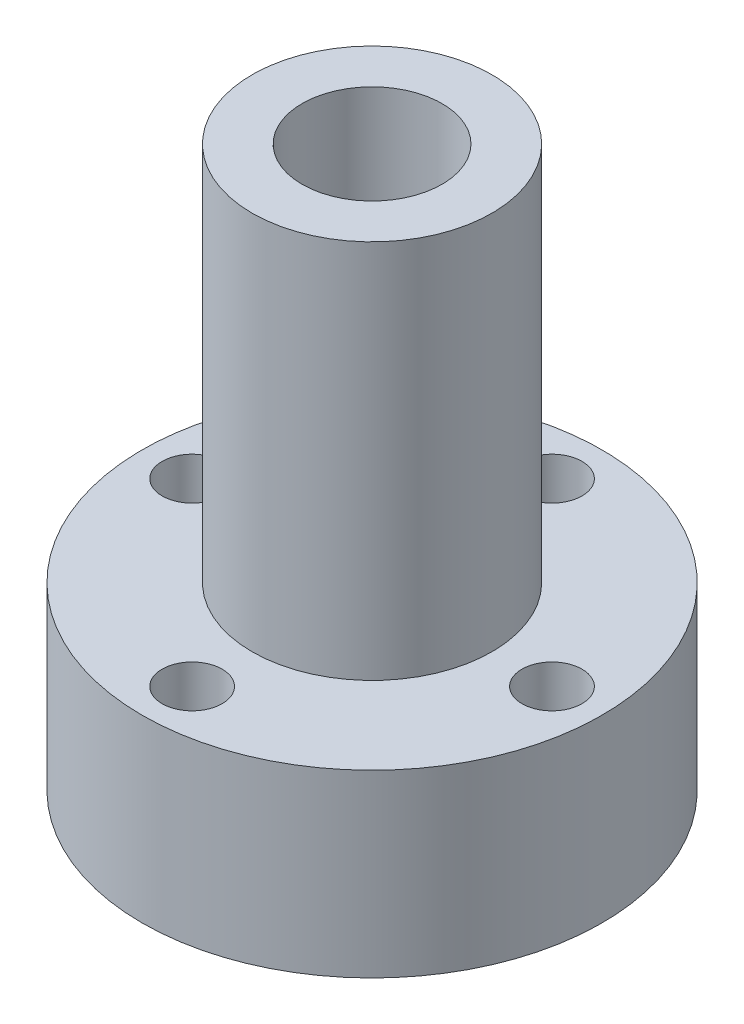
SolidWorks part; units mm, degrees
material "1023 Arkusz stali węglowej (SS)"
ref_plane "Płaszczyzna przednia" through (0, 0, 0) normal (0, 0, 1) x (1, 0, 0)
ref_plane "Płaszczyzna górna" through (0, 0, 0) normal (0, 1, 0) x (1, 0, 0)
ref_plane "Płaszczyzna prawa" through (0, 0, 0) normal (1, 0, 0) x (0, 0, -1)
sketch "Szkic1" plane through (0, 0, 0) normal (0, 0, 1) x (1, 0, 0)
  line L0 (0, 0) -> (0, -37.7643) construction
  line L10 (-23, -9.5) -> (-12, -9.5)
  line L11 (-12, -9.5) -> (-12, 28.5)
  line L12 (-7, 28.5) -> (-7, -29.5)
  line L13 (-7, 28.5) -> (-12, 28.5)
  line L14 (-23, -27.5) -> (-23, -9.5)
  line L15 (-10, -27.5) -> (-10, -29.5)
  line L16 (-10, -29.5) -> (-7, -29.5)
  line L17 (-23, -27.5) -> (-10, -27.5)
revolve "Obrót1" add sketch "Szkic1" angle 360 about L0
sketch "Szkic2" plane through (0, -27.5, 0) normal (0, -1, 0) x (1, 0, 0)
  circle A0 centre (0, 18) radius 3
  circle A1 centre (18, 0) radius 3
  circle A2 centre (0, -18) radius 3
  circle A3 centre (-18, 0) radius 3
  point P12 (0, 0)
  dimension "D1" = 6
  dimension "D2" = 18
  dimension "D3" = 4
extrude "Wytnij-wyciągnięcie1" cut sketch "Szkic2" against normal through all
